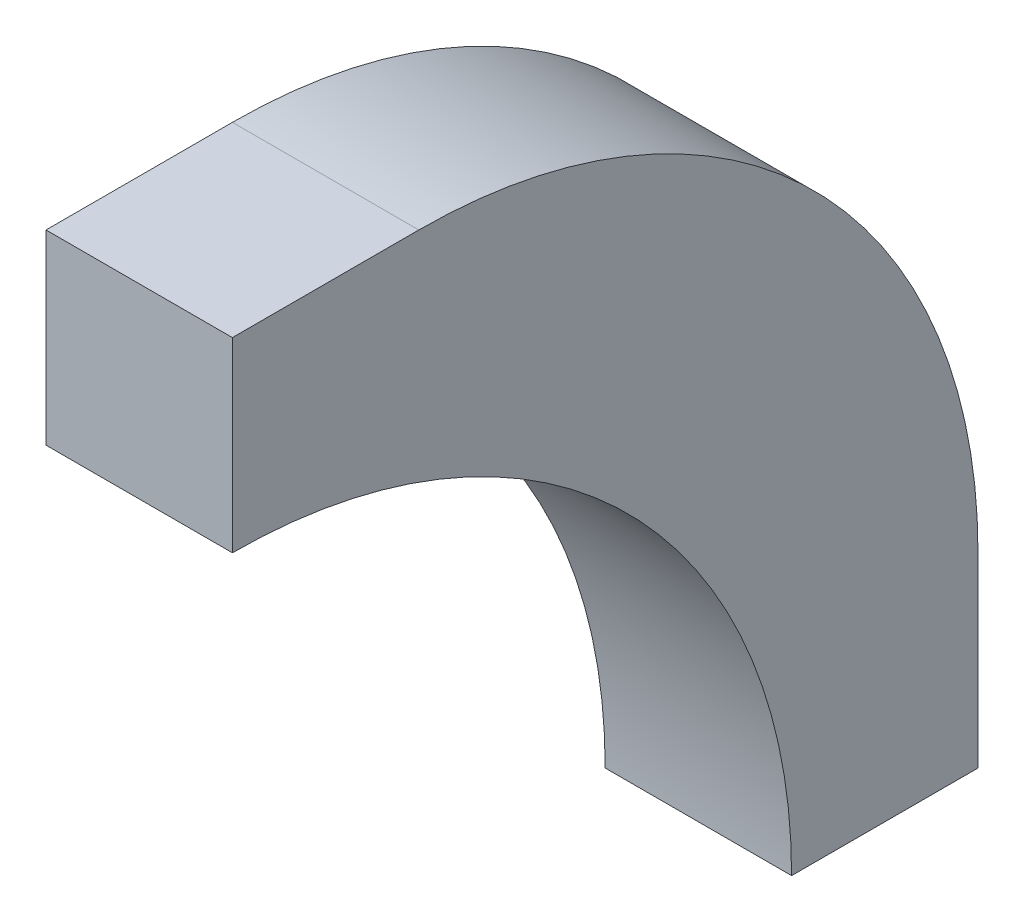
SolidWorks part; units mm, degrees
ref_plane "Front Plane" through (0, 0, 0) normal (0, 0, 1) x (1, 0, 0)
ref_plane "Top Plane" through (0, 0, 0) normal (0, 1, 0) x (1, 0, 0)
ref_plane "Right Plane" through (0, 0, 0) normal (1, 0, 0) x (0, 0, -1)
sketch "Sketch1" plane through (0, 0, 0) normal (1, 0, 0) x (0, 0, -1)
  line L0 (0, 0) -> (0, 50.8)
  line L1 (0, 50.8) -> (-50.8, 50.8)
  line L2 (-50.8, 50.8) -> (-50.8, 38.1)
  line L3 (-50.8, 38.1) -> (-12.7, 38.1)
  line L4 (-12.7, 38.1) -> (-12.7, 0)
  line L5 (-12.7, 0) -> (0, 0)
extrude "Boss-Extrude1" add sketch "Sketch1" along normal blind 12.7
fillet "Fillet1" radius 38.1 1 edges at (6.35, 38.1, 12.7)
fillet "Fillet2" radius 38.1 1 edges at (6.35, 50.8, 0)
